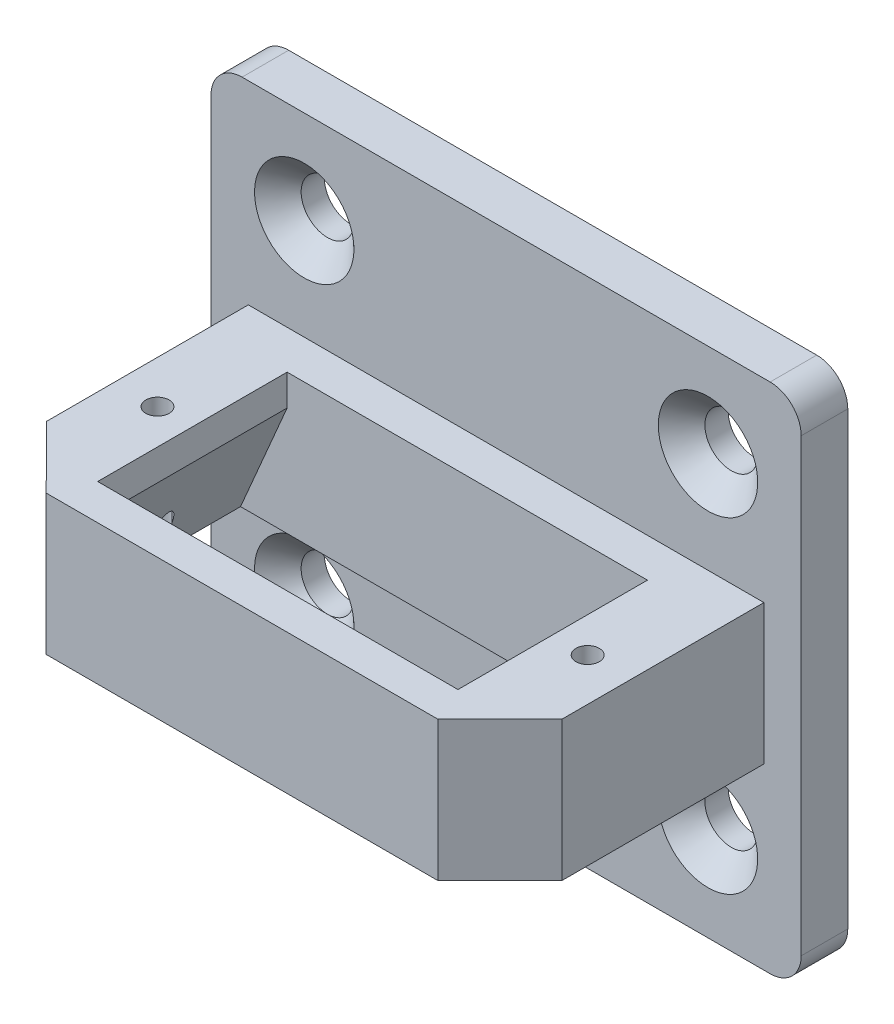
SolidWorks part; units mm, degrees
ref_plane "Front Plane" through (0, 0, 0) normal (0, 0, 1) x (1, 0, 0)
ref_plane "Top Plane" through (0, 0, 0) normal (0, 1, 0) x (1, 0, 0)
ref_plane "Right Plane" through (0, 0, 0) normal (1, 0, 0) x (0, 0, -1)
sketch "Sketch1" plane through (0, 0, 0) normal (0, 0, 1) x (1, 0, 0)
  line L1 (-19, -16.5) -> (19, -16.5)
  line L2 (-19, -16.5) -> (-19, 16.5)
  line L3 (-19, 16.5) -> (19, 16.5)
  line L4 (19, -16.5) -> (19, 16.5)
  line L5 (-19, -16.5) -> (19, 16.5) construction
  line L6 (-19, 16.5) -> (19, -16.5) construction
  circle A0 centre (-13, 10.5) radius 1.7
  circle A1 centre (13, 10.5) radius 1.7
  circle A2 centre (13, -10.5) radius 1.7
  circle A3 centre (-13, -10.5) radius 1.7
  point P12 (0, 0)
  dimension "D1" = 3.4
  dimension "D2" = 6
  dimension "D3" = 6
extrude "Boss-Extrude1" add sketch "Sketch1" along normal blind 3
ref_plane "Plane1" through (0, 0, 0) normal (0, -1, 0) x (-1, 0, 0)
sketch "Sketch3" plane through (0, 0, 0) normal (0, -1, 0) x (-1, 0, 0)
  line L0 (0, 0) -> (0, -3) construction
  line L1 (19, -3) -> (19, 0) construction
  line L2 (-11.6, -17.7) -> (11.6, -17.7)
  line L3 (-11.6, -17.7) -> (-11.6, -5.5)
  line L4 (-11.6, -5.5) -> (11.6, -5.5)
  line L5 (11.6, -17.7) -> (11.6, -5.5)
  line L6 (-11.6, -17.7) -> (11.6, -5.5) construction
  line L7 (-11.6, -5.5) -> (11.6, -17.7) construction
  line L8 (0, -3) -> (0, -11.6) construction
  line L9 (-13.85, -11.6) -> (13.85, -11.6) construction
  line L10 (16.6, -3) -> (16.6, -16)
  line L13 (-16.6, -3) -> (-16.6, -16)
  line L14 (16.6, -3) -> (-16.6, -3)
  line L15 (0, -11.6) -> (0, -20) construction
  line L16 (12.6128, -20) -> (-12.6128, -20)
  line L17 (16.6, -16) -> (12.6128, -20)
  line L18 (-12.6128, -20) -> (-16.6, -16)
  line L19 (19, -3) -> (-19, -3) construction
  circle A0 centre (-13.85, -11.6) radius 0.75
  circle A1 centre (13.85, -11.6) radius 0.75
  dimension "D4" = 1.5
  dimension "D1" = 23.2
  dimension "D2" = 12.2
  dimension "D3" = 27.7
  dimension "D5" = 5
  dimension "D6" = 2.5
  dimension "D7" = 2.3
  dimension "D8" = 13
extrude "Boss-Extrude2" add sketch "Sketch3" along normal blind 5 and the other way blind 4
fillet "Fillet1" radius 2 4 edges at (-19, 16.5, 1.5) (-19, -16.5, 1.5) (19, 16.5, 1.5) (19, -16.5, 1.5)
chamfer "Chamfer1" distance 1.5 angle 45 4 edges at (-11.3, 10.5, 3) (-11.3, -10.5, 3) (14.7, -10.5, 3) (14.7, 10.5, 3)
chamfer "Chamfer2" distance 3 distance2 7 1 edges at (-11.6, -5, 11.6) first distance on face at (13.85, -5, 10.85)
